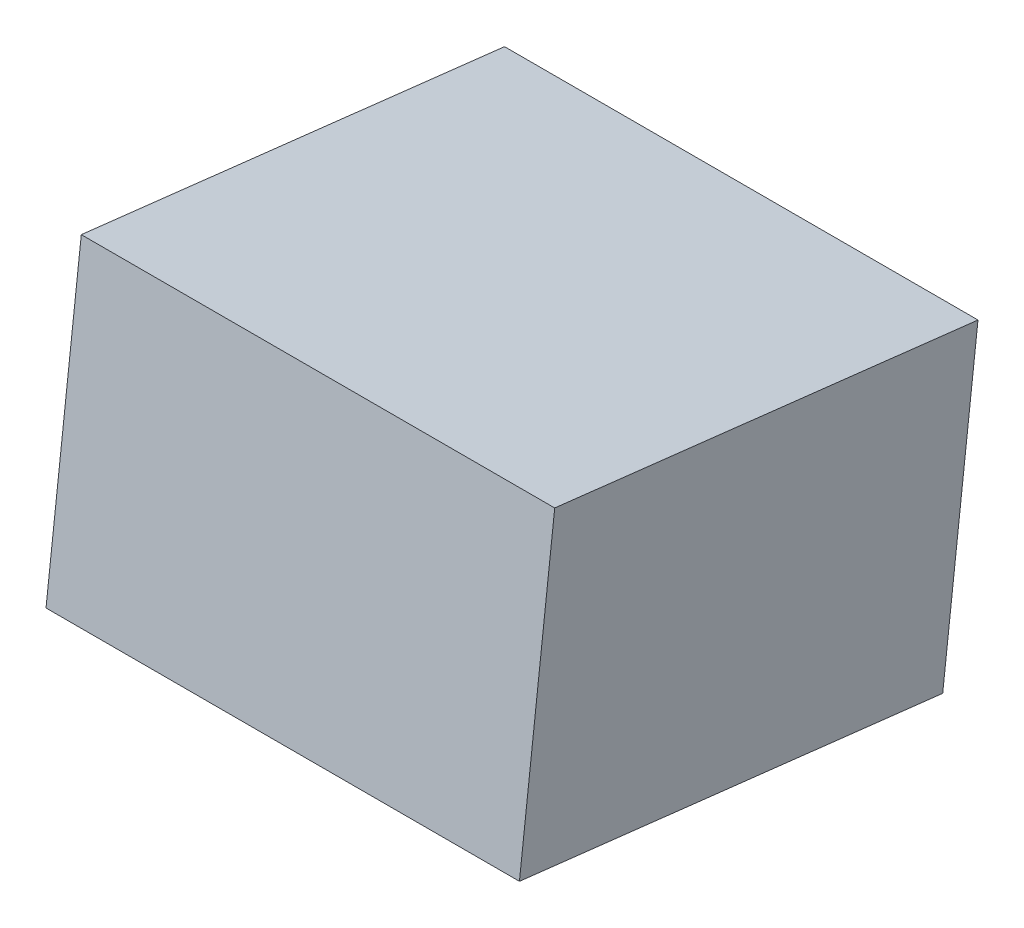
SolidWorks part; units mm, degrees
ref_plane "Front Plane" through (0, 0, 0) normal (0, 0, 1) x (1, 0, 0)
ref_plane "Top Plane" through (0, 0, 0) normal (0, 1, 0) x (1, 0, 0)
ref_plane "Right Plane" through (0, 0, 0) normal (1, 0, 0) x (0, 0, -1)
sketch "Sketch1" plane through (0, 358.8799, -41.4225) normal (0, 0.9934, -0.1147) x (1, 0, 0)
  line L1 (-231.6731, 121.357) -> (-31.6731, 121.357)
  line L2 (-231.6731, 121.357) -> (-231.6731, 301.357)
  line L3 (-231.6731, 301.357) -> (-31.6731, 301.357)
  line L4 (-31.6731, 121.357) -> (-31.6731, 301.357)
  line L5 (-231.6731, 121.357) -> (-31.6731, 301.357) construction
  line L6 (-231.6731, 301.357) -> (-31.6731, 121.357) construction
  point P0 (-131.6731, 211.357)
  dimension "D1" = 180
  dimension "D2" = 200
extrude "Boss-Extrude1" add sketch "Sketch1" along normal blind 130
